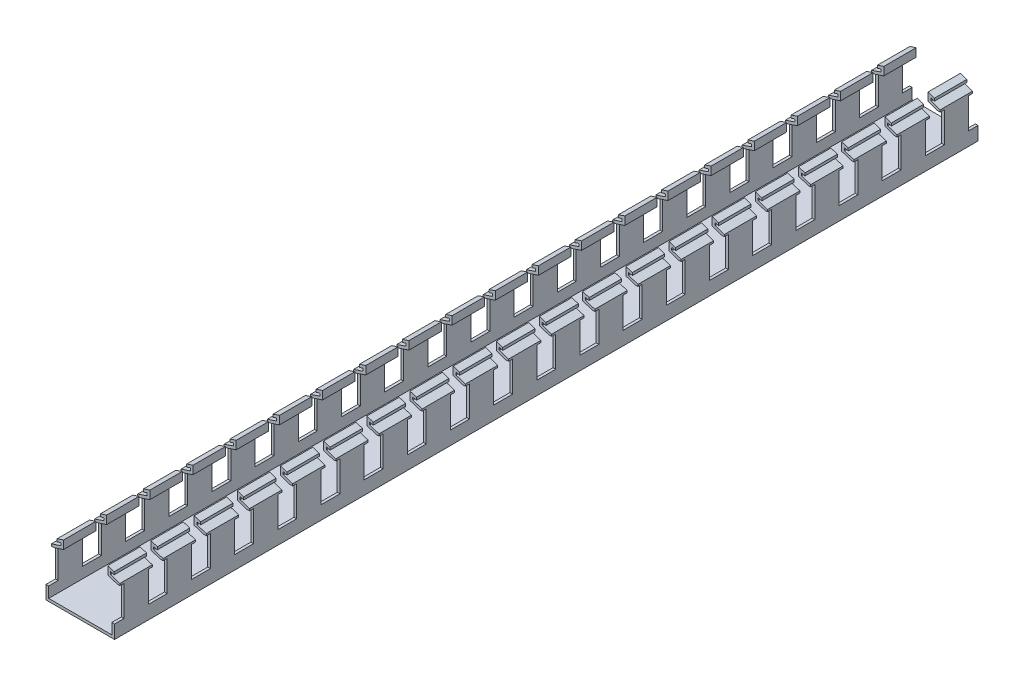
SolidWorks part; units mm, degrees
ref_plane "Alzado" through (0, 0, 0) normal (0, 0, 1) x (1, 0, 0)
ref_plane "Planta" through (0, 0, 0) normal (0, 1, 0) x (1, 0, 0)
ref_plane "Vista lateral" through (0, 0, 0) normal (1, 0, 0) x (0, 0, -1)
sketch "Croquis2" plane through (0, 0, 0) normal (0, 0, 1) x (1, 0, 0)
  line L0 (-12.7, 0) -> (12.7, 0)
  line L1 (0, 0) -> (0, 14.1113) construction
  line L2 (-12.7, 0) -> (-12.7, 17)
  line L4 (8.2, 17.4459) -> (11.7, 16.2792)
  line L5 (8.2, 20.5) -> (8.2, 17.4459)
  line L6 (10.5717, 19.7094) -> (8.2, 20.5)
  line L7 (10.5717, 18.7094) -> (10.5717, 19.7094)
  line L8 (9.2, 18.8892) -> (9.2, 18.3108)
  line L9 (10.5717, 18.7094) -> (9.4632, 19.0789)
  line L10 (-9.3368, 18.1211) -> (-12.7, 17)
  line L11 (-10.5717, 18.7094) -> (-9.4632, 19.0789)
  line L12 (-9.2, 18.8892) -> (-9.2, 18.3108)
  line L13 (9.3368, 18.1211) -> (12.7, 17)
  line L14 (12.7, 0) -> (12.7, 17)
  line L15 (11.7, 16.2792) -> (11.7, 1)
  line L16 (-10.5717, 18.7094) -> (-10.5717, 19.7094)
  line L18 (-10.5717, 19.7094) -> (-8.2, 20.5)
  line L19 (-8.2, 20.5) -> (-8.2, 17.4459)
  line L20 (-8.2, 17.4459) -> (-11.7, 16.2792)
  line L21 (-11.7, 16.2792) -> (-11.7, 1)
  line L22 (-11.7, 1) -> (11.7, 1)
  arc A0 (9.3368, 18.1211) -> (9.2, 18.3108) centre (9.4, 18.3108) cw
  arc A1 (9.2, 18.8892) -> (9.4632, 19.0789) centre (9.4, 18.8892) cw
  arc A4 (-9.2, 18.8892) -> (-9.4632, 19.0789) centre (-9.4, 18.8892) ccw
  arc A5 (-9.3368, 18.1211) -> (-9.2, 18.3108) centre (-9.4, 18.3108) ccw
  dimension "D8" = 0.2
  dimension "D1" = 25.4
  dimension "D2" = 1
  dimension "D3" = 1
  dimension "D4" = 1
  dimension "D5" = 1
  dimension "D6" = 1
  dimension "D7" = 20.5
  dimension "D9" = 8.2
  dimension "D10" = 2.5
  dimension "D11" = 71.565
  dimension "D12" = 3.0541
extrude "Saliente-Extruir1" add sketch "Croquis2" along normal mid plane 16
sketch "Croquis3" plane through (0, 0, 0) normal (1, 0, 0) x (0, 0, -1)
  line L0 (0, 0) -> (0, 24.3686) construction
  line L1 (-8, 0) -> (8, 0) construction
  line L2 (-8, 5) -> (-4.5, 5)
  line L3 (-8, 0) -> (-8, 17) construction
  line L4 (-4.5, 5) -> (-4.5, 16.2792)
  line L5 (-4.5, 16.2792) -> (-6, 16.2792)
  line L6 (-6, 16.2792) -> (-6, 20.5)
  line L7 (-8, 5) -> (-8, 20.5)
  line L8 (-8, 20.5) -> (-6, 20.5)
  line L10 (-8, 20.5) -> (8, 20.5) construction
  line L11 (8, 20.5) -> (6, 20.5)
  line L12 (8, 5) -> (8, 20.5)
  line L13 (6, 16.2792) -> (6, 20.5)
  line L14 (4.5, 16.2792) -> (6, 16.2792)
  line L15 (4.5, 5) -> (4.5, 16.2792)
  line L16 (8, 5) -> (4.5, 5)
  line L17 (-8, 16.2792) -> (8, 16.2792) construction
  dimension "D1" = 5
  dimension "D2" = 3.5
  dimension "D3" = 2
extrude "Cortar-Extruir1" cut sketch "Croquis3" against normal mid plane 66
pattern_linear "MatrizL1" count 20 spacing 16 along (0, 0, -1) of "Saliente-Extruir1", "Cortar-Extruir1"
